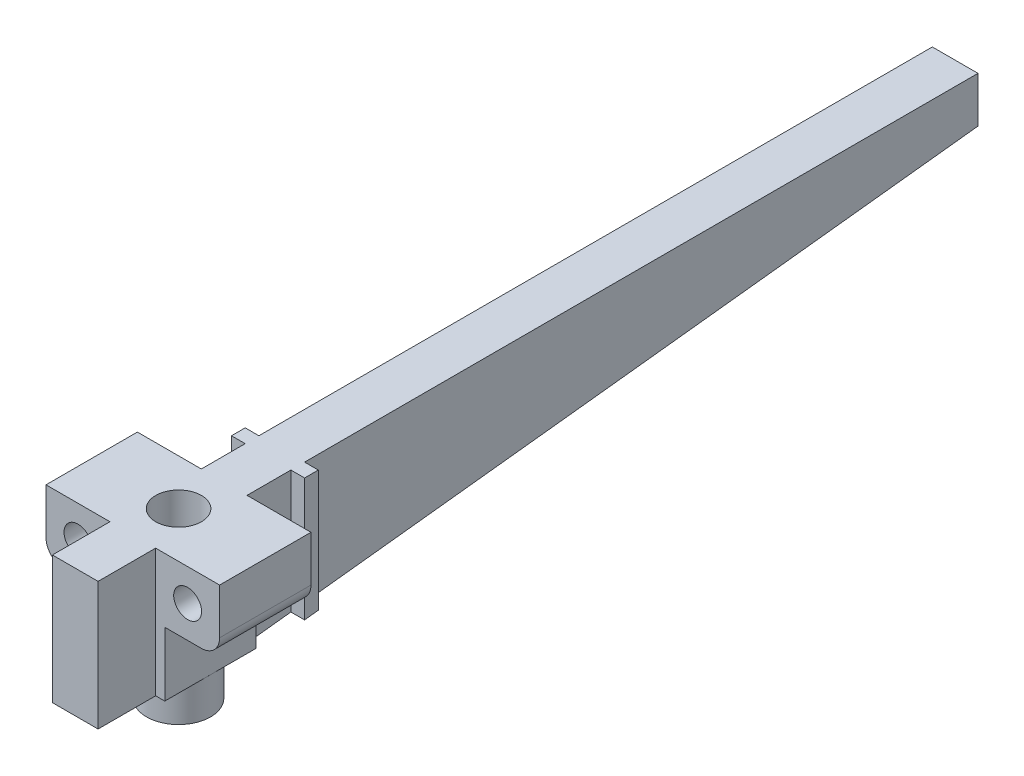
SolidWorks part; units mm, degrees
ref_plane "前视基准面" through (0, 0, 0) normal (0, 0, 1) x (1, 0, 0)
ref_plane "上视基准面" through (0, 0, 0) normal (0, 1, 0) x (1, 0, 0)
ref_plane "右视基准面" through (0, 0, 0) normal (1, 0, 0) x (0, 0, -1)
other "Configuration Table"
sketch "草图1" plane through (0, 0, 0) normal (0, 0, 1) x (1, 0, 0)
  line L0 (-4.6095, 6.3014) -> (-4.6095, 1.3014)
  line L5 (-2.6095, -0.6986) -> (1.3905, -0.6986)
  line L6 (1.3905, -0.6986) -> (1.3905, -7.6986)
  line L7 (1.3905, -7.6986) -> (8.3905, -7.6986)
  line L8 (8.3905, -7.6986) -> (8.3905, -0.6986)
  line L9 (8.3905, -0.6986) -> (12.3905, -0.6986)
  line L10 (14.3905, 1.3014) -> (14.3905, 6.3014)
  line L11 (14.3905, 6.3014) -> (-4.6095, 6.3014)
  arc A0 (-4.6095, 1.3014) -> (-2.6095, -0.6986) centre (-2.6095, 1.3014) ccw
  arc A1 (12.3905, -0.6986) -> (14.3905, 1.3014) centre (12.3905, 1.3014) ccw
  circle A2 centre (10.8905, 2.8014) radius 1.525
  circle A3 centre (-1.1095, 2.8014) radius 1.525
extrude "凸台-拉伸1" add sketch "草图1" along normal blind 10
ref_plane "基准面1" through (4.8905, 0, 0) normal (1, 0, 0) x (0, 0, -1)
sketch "草图3" plane through (4.8905, 0, 0) normal (1, 0, 0) x (0, 0, -1)
  line L0 (0, 6.3014) -> (80, 6.3014)
  line L1 (80, 6.3014) -> (80, 1.3014)
  line L2 (80, 1.3014) -> (0, -7.6986)
  line L3 (0, 6.3014) -> (0, -7.6986)
  dimension "D1" = 80
  dimension "D2" = 5
extrude "凸台-拉伸2" add sketch "草图3" along normal blind 2.5 and the other way blind 2.5
sketch "草图4" plane through (0, 0, 10) normal (0, 0, 1) x (1, 0, 0)
  line L0 (4.8905, 6.3014) -> (4.8905, 8.8738) construction
  line L2 (14.3905, 6.3014) -> (-4.6095, 6.3014) construction
  line L3 (2.3905, 6.3014) -> (7.3905, 6.3014)
  line L4 (2.3905, 6.3014) -> (2.3905, -7.6986)
  line L5 (2.3905, -7.6986) -> (7.3905, -7.6986)
  line L6 (7.3905, 6.3014) -> (7.3905, -7.6986)
  line L7 (1.3905, -7.6986) -> (8.3905, -7.6986) construction
  point P6 (4.8905, 6.3014)
  point P9 (4.8905, 6.3014)
  dimension "D1" = 5
extrude "凸台-拉伸3" add sketch "草图4" along normal blind 6.3
sketch "草图5" plane through (0, 6.3014, 0) normal (0, 1, 0) x (1, 0, 0)
  line L0 (-4.6095, -5) -> (49995.3905, -5) construction
  line L1 (-4.6095, -10) -> (-4.6095, 0) construction
  line L2 (4.8905, -20) -> (4.8905, 49980) construction
  line L3 (7.3905, -16.3) -> (2.3905, -16.3) construction
  circle A0 centre (4.9009, -5) radius 2.5
  point P4 (-4.6095, -5)
  point P9 (4.8905, -16.3)
  dimension "D1" = 5
extrude "切除-拉伸1" cut sketch "草图5" against normal up to next
sketch "草图6" plane through (7.3905, 0, 0) normal (1, 0, 0) x (0, 0, -1)
  line L0 (4.8, 6.3014) -> (4.8, -7.1586)
  line L1 (6.3, 6.3014) -> (6.3, -6.9899)
  line L4 (0, 6.3014) -> (0, -7.6986)
  line L5 (0, -7.6986) -> (80, 1.3014)
  line L6 (80, 1.3014) -> (80, 6.3014)
  line L7 (80, 6.3014) -> (0, 6.3014)
  line L8 (0, 6.3014) -> (0, -7.6986)
  line L9 (0, -7.6986) -> (6.3, -6.9899)
  line L11 (6.3, 6.3014) -> (0, 6.3014)
  line M7 (0, -7.6986) -> (80, 1.3014)
  line M9 (80, 6.3014) -> (0, 6.3014)
  dimension "D2" = 1.5
  dimension "D3" = 6.3
  dimension "D1" = 0
extrude "凸台-拉伸5" add sketch "草图6" along normal blind 1.5 contours L1 L0 M9 M7 region at (7.3905, -0.3865, -5.5484)
mirror "镜向1" about plane through (4.8905, 0, 0) normal (1, 0, 0) of "凸台-拉伸5"
sketch "草图7" plane through (0, -7.6986, 0) normal (0, -1, 0) x (1, 0, 0)
  circle A0 centre (4.9009, 5) radius 3.5
  circle A1 centre (4.9009, 5) radius 3.05
  dimension "D1" = 7
  dimension "D2" = 6.1
extrude "凸台-拉伸6" add sketch "草图7" along normal blind 4
